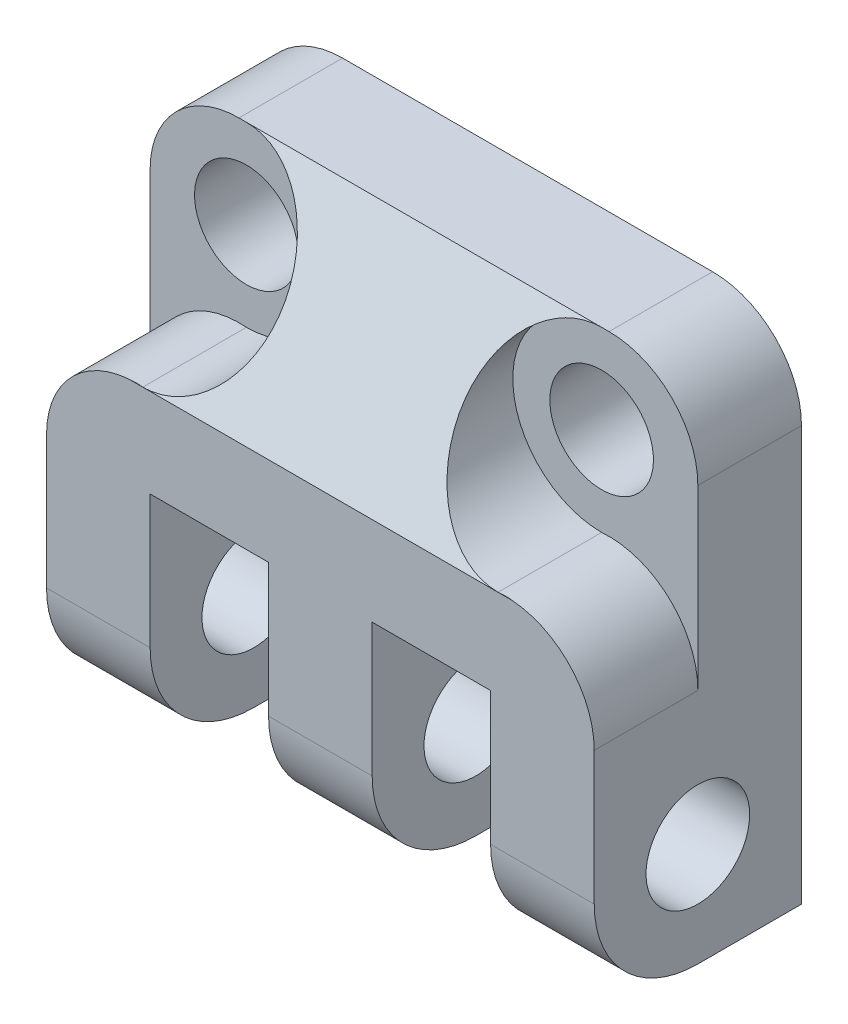
SolidWorks part; units mm, degrees
ref_plane "Front Plane" through (0, 0, 0) normal (0, 0, 1) x (1, 0, 0)
ref_plane "Top Plane" through (0, 0, 0) normal (0, 1, 0) x (1, 0, 0)
ref_plane "Right Plane" through (0, 0, 0) normal (1, 0, 0) x (0, 0, -1)
sketch "Sketch1" plane through (0, 0, 0) normal (0, 1, 0) x (1, 0, 0)
  line L1 (-9.25, 4.5) -> (9.25, 4.5)
  line L2 (-9.25, 4.5) -> (-9.25, -4.5)
  line L3 (-9.25, -4.5) -> (9.25, -4.5)
  line L4 (9.25, 4.5) -> (9.25, -4.5)
  line L5 (-9.25, 4.5) -> (9.25, -4.5) construction
  line L6 (-9.25, -4.5) -> (9.25, 4.5) construction
  point P0 (0, 0)
  dimension "D1" = 18.5
  dimension "D2" = 9
extrude "Boss-Extrude1" add sketch "Sketch1" along normal blind 3.5
sketch "Sketch2" plane through (0, 3.5, 0) normal (0, 1, 0) x (1, 0, 0)
  line L0 (0, 4.5) -> (0, -4.5) construction
  line L1 (9.25, 4.5) -> (-9.25, 4.5) construction
  line L2 (-9.25, -4.5) -> (9.25, -4.5) construction
  line L3 (-9.25, 1.5) -> (9.25, 1.5) construction
  line L4 (-9.25, 4.5) -> (-9.25, -4.5) construction
  line L5 (9.25, -4.5) -> (9.25, 4.5) construction
  circle A0 centre (-6, 1.5) radius 1.75
  circle A1 centre (6, 1.5) radius 1.75
  dimension "D1" = 3.5
  dimension "D2" = 12
  dimension "D3" = 6
extrude "Cut-Extrude1" cut sketch "Sketch2" against normal through all
sketch "Sketch4" plane through (0, 0, 0) normal (0, -1, 0) x (1, 0, 0)
  line L0 (0, 4.5) -> (0, -4.5) construction
  line L1 (-9.25, 4.5) -> (9.25, 4.5) construction
  line L2 (9.25, -4.5) -> (-9.25, -4.5) construction
  line L3 (-1.75, 12.5) -> (1.75, 12.5)
  line L4 (-6, -4.5) -> (6, -4.5)
  line L5 (-5.75, 4.5) -> (-1.75, 4.5)
  line L6 (9.25, 12.5) -> (9.25, 4.5)
  line L7 (0, 4.5) -> (0, 12.5) construction
  line L8 (5.75, 12.5) -> (9.25, 12.5)
  line L9 (5.75, 4.5) -> (5.75, 12.5)
  line L10 (1.75, 4.5) -> (1.75, 12.5)
  line L11 (5.75, 4.5) -> (1.75, 4.5)
  line L12 (-1.75, 4.5) -> (-1.75, 12.5)
  line L14 (-5.75, 4.5) -> (-5.75, 12.5)
  line L15 (-5.75, 12.5) -> (-9.25, 12.5)
  line L16 (-9.25, 12.5) -> (-9.25, 4.5)
  arc A0 (-3, -1.5) -> (-6, -4.5) centre (-6, -1.5) cw
  arc A1 (-3, -1.5) -> (-6, 1.5) centre (-6, -1.5) ccw
  arc A2 (-6, 1.5) -> (-9.25, 4.5) centre (-6.2404, 4.5) cw
  arc A3 (6, 1.5) -> (9.25, 4.5) centre (6.2404, 4.5) ccw
  arc A4 (3, -1.5) -> (6, 1.5) centre (6, -1.5) cw
  arc A5 (3, -1.5) -> (6, -4.5) centre (6, -1.5) ccw
  point P29 (0, 12.5)
  dimension "D1" = 3
  dimension "D2" = 3.5
  dimension "D3" = 4
  dimension "D4" = 8
extrude "Boss-Extrude3" add sketch "Sketch4" against normal blind 7
sketch "Sketch7" plane through (9.25, 0, 0) normal (1, 0, 0) x (0, 0, -1)
  line L1 (-12.5, 7) -> (-12.5, 0) construction
  line L3 (-9, 7) -> (-12.5, 7)
  line L4 (-12.5, 7) -> (-12.5, 3.5)
  arc A0 (-9, 7) -> (-12.5, 3.5) centre (-9, 3.5) ccw
  point P4 (-12.5, 3.5)
extrude "Cut-Extrude3" cut sketch "Sketch7" against normal through all contours A0 L3 L4 | A0 L4 | A0 L4 L3 region at (9.25, 6.2182, 11.7182)
sketch "Sketch8" plane through (9.25, 0, 0) normal (1, 0, 0) x (0, 0, -1)
  circle A0 centre (-9, 3.5) radius 1.75
  arc A3 (-9, 7) -> (-12.5, 3.5) centre (-9, 3.5) ccw construction
  dimension "D1" = 3.5
extrude "Cut-Extrude4" cut sketch "Sketch8" against normal through all
sketch "Sketch6" plane through (9.25, 0, 0) normal (1, 0, 0) x (0, 0, -1)
  line L0 (-1.5, 7) -> (4.5, 3.5)
  line L1 (4.5, 3.5) -> (4.5, 7)
  line L2 (4.5, 7) -> (-1.5, 7)
fillet "Fillet1" radius 3 2 edges at (-9.25, 1.75, -4.5) (9.25, 1.75, -4.5)
extrude "Cut-Extrude5" cut sketch "Sketch6" against normal through all
move or copy body "Body-Move/Copy1" bodies to move or copy 108 copy no rotation origin (0, 3.5, 4) rotation axis (1, 0, 0) rotation angle 90
